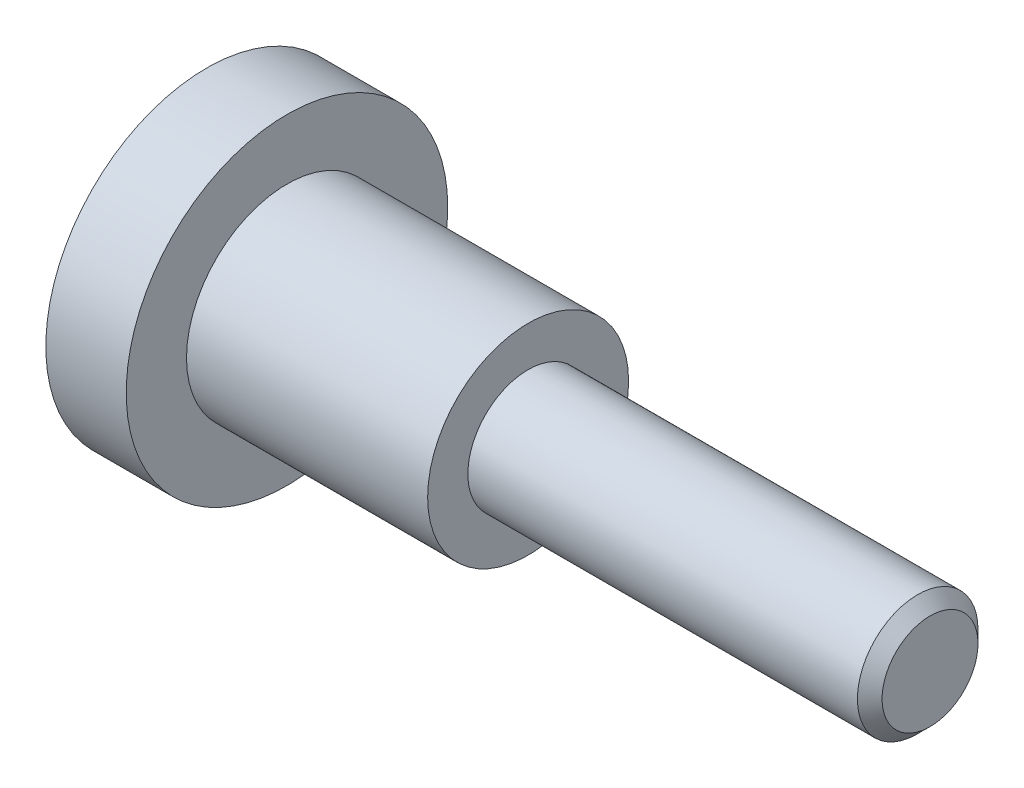
SolidWorks part; units mm, degrees
ref_plane "Front Plane" through (0, 0, 0) normal (0, 0, 1) x (1, 0, 0)
ref_plane "Top Plane" through (0, 0, 0) normal (0, 1, 0) x (1, 0, 0)
ref_plane "Right Plane" through (0, 0, 0) normal (1, 0, 0) x (0, 0, -1)
sketch "Sketch1" plane through (0, 0, 0) normal (0, 0, 1) x (1, 0, 0)
  line L0 (-8, 4) -> (-8, 0)
  line L1 (-8, 0) -> (-6, 0)
  line L2 (-6, 0) -> (-6, 4)
  line L3 (-6, 4) -> (-8, 4)
  line L4 (-8, 0) -> (-6, 0) construction
revolve "Revolve1" add sketch "Sketch1" angle 360 about L4 reverse direction yes
sketch "Sketch2" plane through (-6, 0, 0) normal (1, 0, 0) x (0, 0, -1)
  circle A0 centre (0, 0) radius 2.5
extrude "Boss-Extrude1" add sketch "Sketch2" along normal blind 6
sketch "Sketch3" plane through (0, 0, 0) normal (1, 0, 0) x (0, 0, -1)
  circle A0 centre (0, 0) radius 1.5
extrude "Boss-Extrude2" add sketch "Sketch3" along normal blind 10
sketch "Sketch4" plane through (-8, 0, 0) normal (-1, 0, 0) x (0, 0, 1)
  line L0 (0, -1.1547) -> (1, -0.5774)
  line L1 (1, -0.5774) -> (1, 0.5774)
  line L2 (1, 0.5774) -> (0, 1.1547)
  line L3 (0, 1.1547) -> (-1, 0.5774)
  line L4 (-1, 0.5774) -> (-1, -0.5774)
  line L5 (-1, -0.5774) -> (0, -1.1547)
extrude "Cut-Extrude1" cut sketch "Sketch4" against normal blind 2
sketch "Sketch5" plane through (0, 0, 0) normal (0, 0, 1) x (1, 0, 0)
  line L0 (-6, 1) -> (-6, 0)
  line L1 (-6, 0) -> (-5.4226, 0)
  line L2 (-5.4226, 0) -> (-6, 1)
  line L3 (-6, 0) -> (-5.4226, 0) construction
revolve "Cut-Revolve1" cut sketch "Sketch5" angle 360 about L3 reverse direction yes
chamfer "Chamfer1" distance 0.3065 angle 45 1 edges at (10, 0, -1.5)
ref_axis "Axis1" through (0, 0, 0) along (-1, 0, 0)
ref_axis "Axis2" through (9.6935, 0, 0) along (-1, 0, 0)
